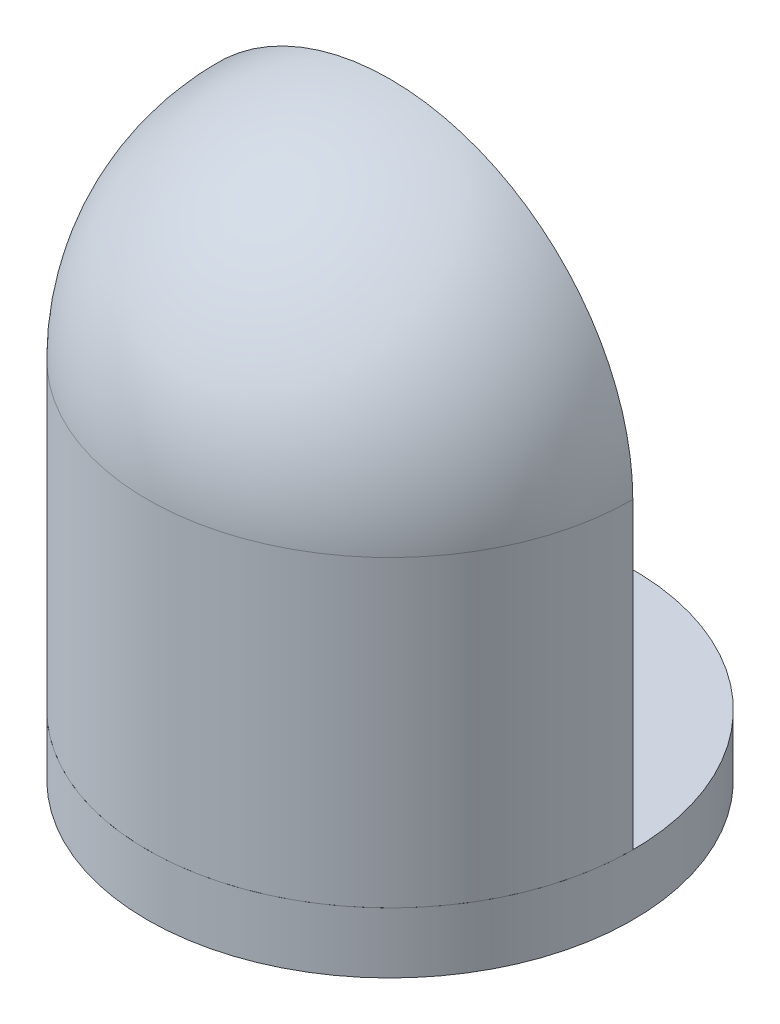
SolidWorks part; units mm, degrees
material "1060 合金"
ref_plane "前视基准面" through (0, 0, 0) normal (0, 0, 1) x (1, 0, 0)
ref_plane "上视基准面" through (0, 0, 0) normal (0, 1, 0) x (1, 0, 0)
ref_plane "右视基准面" through (0, 0, 0) normal (1, 0, 0) x (0, 0, -1)
sketch "草图1" plane through (0, 0, 0) normal (0, 1, 0) x (1, 0, 0)
  circle A0 centre (0, 0) radius 40
  dimension "D1" = 80
extrude "凸台-拉伸1" add sketch "草图1" along normal blind 10
sketch "草图2" plane through (0, 0, 0) normal (0, 0, 1) x (1, 0, 0)
  line L0 (0, 111.9766) -> (0, -14.4138) construction
  line L1 (-40, 10) -> (40, 10)
  line L2 (-40, 10) -> (-40, 60)
  line L3 (40, 10) -> (40, 60)
  circle A0 centre (0, 60) radius 40
  dimension "D1" = 80
  dimension "D2" = 60
revolve "旋转1" add sketch "草图2" angle 180 about L0 region at (16.9765, 60, 0) region at (25.1111, 21.4365, 0)
